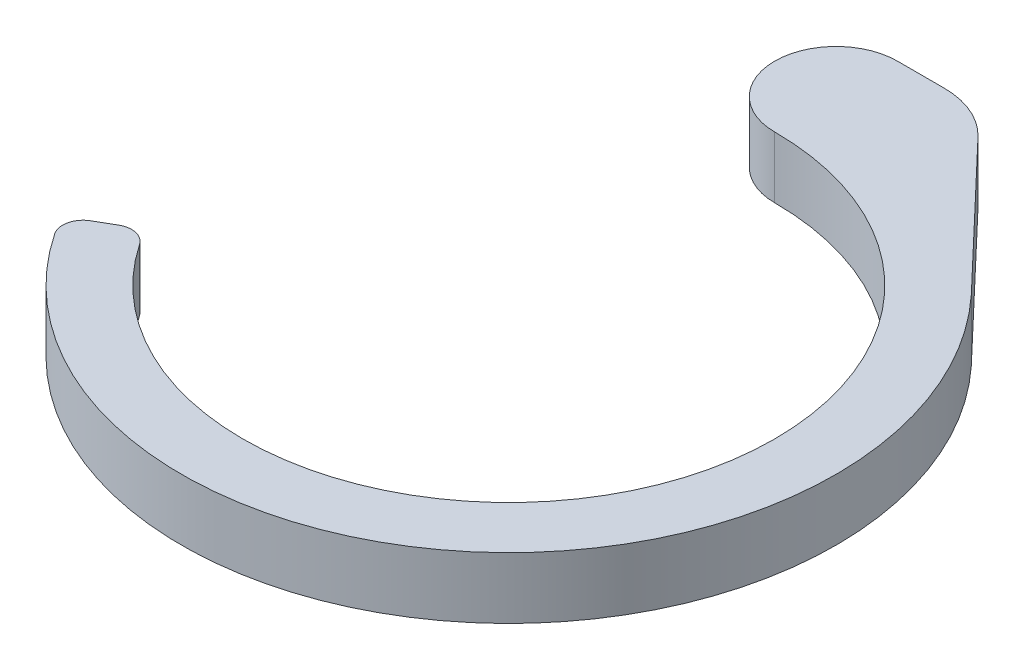
SolidWorks part; units mm, degrees
ref_plane "正面" through (0, 0, 0) normal (0, 0, 1) x (1, 0, 0)
ref_plane "平面" through (0, 0, 0) normal (0, 1, 0) x (1, 0, 0)
ref_plane "右側面" through (0, 0, 0) normal (1, 0, 0) x (0, 0, -1)
sketch "ｽｹｯﾁ2" plane through (0, 0, 0) normal (0, 1, 0) x (1, 0, 0)
  line L1 (-1.8089, 2.6033) -> (0, 0)
  line L2 (-60.4669, -34.9106) -> (-64.8074, -37.4166)
  line L4 (0, 95) -> (11.4274, 95)
  line L5 (25.9115, 88.7917) -> (58.5757, 54.4875)
  arc A0 (-66.4612, -44.5298) -> (57.2894, 55.8384) centre (0, 0) ccw
  arc A1 (-53.8264, -36.4378) -> (0, 65) centre (0, 0) ccw
  arc A2 (0, 95) -> (0, 65) centre (0, 80) ccw
  arc A3 (11.4274, 95) -> (25.9115, 88.7917) centre (11.4274, 75) cw
  arc A4 (-53.8264, -36.4378) -> (-60.4669, -34.9106) centre (-57.9669, -39.2407) ccw
  arc A5 (-66.4612, -44.5298) -> (-64.8074, -37.4166) centre (-62.3074, -41.7467) cw
  dimension "D1" = 160
  dimension "D2" = 130
  dimension "D4" = 20
  dimension "D5" = 5
  dimension "D6" = 5
extrude "ﾎﾞｽ - 押し出し4" add sketch "ｽｹｯﾁ2" along normal blind 15 contours A5 A0 L5 A3 L4 A2 A1 A4 L2 region at (-57.359, 0, 36.5972)
sketch "ｽｹｯﾁ3" plane through (0, 0, 0) normal (0, -1, 0) x (1, 0, 0)
  circle A0 centre (0, -80) radius 10
  dimension "D1" = 20
extrude "ｶｯﾄ - 押し出し1" cut sketch "ｽｹｯﾁ3" against normal blind 2
